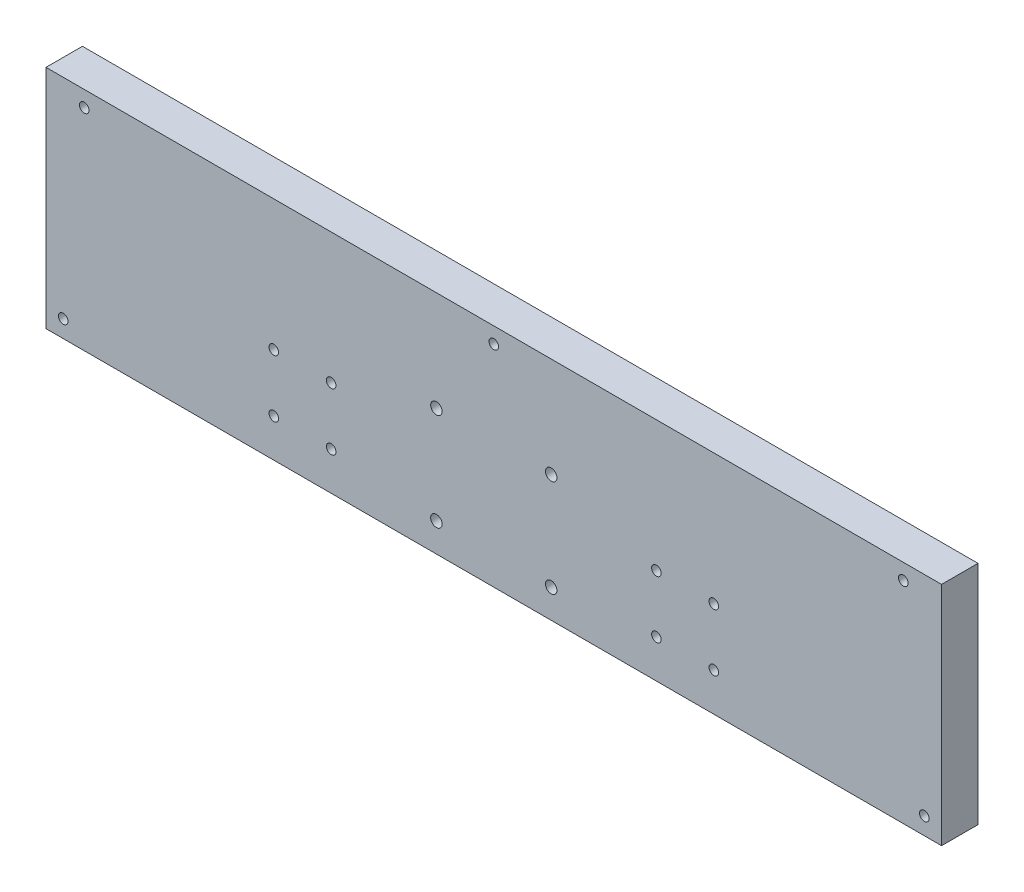
SolidWorks part; units mm, degrees
ref_plane "Front Plane" through (0, 0, 0) normal (0, 0, 1) x (1, 0, 0)
ref_plane "Top Plane" through (0, 0, 0) normal (0, 1, 0) x (1, 0, 0)
ref_plane "Right Plane" through (0, 0, 0) normal (1, 0, 0) x (0, 0, -1)
sketch "Sketch1" plane through (0, 0, 0) normal (0, 0, 1) x (1, 0, 0)
  line L1 (234.05, 0) -> (-234.05, 0)
  line L2 (234.05, 0) -> (234.05, 118.3)
  line L3 (234.05, 118.3) -> (-234.05, 118.3)
  line L4 (-234.05, 0) -> (-234.05, 118.3)
  line L5 (-234.05, 118.3) -> (234.05, 118.3) construction
  dimension "D1" = 118.3
  dimension "D2" = 468.1
extrude "Boss-Extrude1" add sketch "Sketch1" along normal blind 19.05
sketch "Sketch8" plane through (0, 0, 19.05) normal (0, 0, 1) x (1, 0, 0)
  circle A0 centre (-214.05, 110.05) radius 2.5
  circle A1 centre (0, 110.05) radius 2.5
  circle A2 centre (214.05, 110.05) radius 2.5
  circle A3 centre (-225.05, 9) radius 2.5
  circle A4 centre (225.05, 9) radius 2.5
hole_wizard "M5 Clearance Hole1" positions "Sketch2" profile "Sketch3" hole size "M5" standard "ANSI Metric"
sketch "Sketch2" plane through (0, 0, 0) normal (0, 0, -1) x (-1, 0, 0)
  point P0 (-115, 20)
  point P3 (-115, 50)
  point P6 (-85, 50)
  point P9 (-85, 20)
  point P12 (85, 20)
  point P15 (85, 50)
  point P18 (115, 50)
  point P21 (115, 20)
  point P25 (214.05, 110.05)
  point P28 (0, 110.05)
  point P31 (-214.05, 110.05)
  point P34 (-225.05, 9)
  point P37 (225.05, 9)
sketch "Sketch3" plane through (115, 20, 0) normal (1, 0, 0) x (0, 1, 0)
  line L0 (0, 0) -> (0, 30)
  line L1 (0, 30) -> (2.5, 28.4978)
  line L2 (2.5, 28.4978) -> (2.5, 0)
  line L5 (2.5, 0) -> (0, 0)
  line L10 (0, 30) -> (-2.5, 28.4978) construction
  line L11 (0, -6.35) -> (0, 107.95) construction
  dimension "Hole Dia." = 5
  dimension "Hole Depth" = 30
  dimension "Drill Angle" = 118
sketch "Sketch4" plane through (0, 0, 0) normal (0, 0, -1) x (-1, 0, 0)
  circle A0 centre (-30, 15) radius 3 construction
  circle A1 centre (-30, 66) radius 3 construction
  circle A2 centre (30, 66) radius 3 construction
  circle A3 centre (30, 15) radius 3 construction
  circle A4 centre (-30, 15) radius 3
  circle A5 centre (-30, 66) radius 3
  circle A6 centre (30, 66) radius 3
  circle A7 centre (30, 15) radius 3
hole_wizard "M5 Clearance Hole2" positions "Sketch5" profile "Sketch6" hole size "M5" standard "ANSI Metric"
sketch "Sketch5" plane through (0, 0, 0) normal (0, 0, -1) x (-1, 0, 0)
  point P0 (30, 15)
  point P3 (30, 66)
  point P6 (-30, 15)
  point P9 (-30, 66)
sketch "Sketch6" plane through (-30, 15, 0) normal (1, 0, 0) x (0, 1, 0)
  line L0 (0, 0) -> (0, 30)
  line L1 (0, 30) -> (3, 28.1974)
  line L2 (3, 28.1974) -> (3, 0)
  line L5 (3, 0) -> (0, 0)
  line L10 (0, 30) -> (-3, 28.1974) construction
  line L11 (0, -6.35) -> (0, 107.95) construction
  dimension "Hole Dia." = 6
  dimension "Hole Depth" = 30
  dimension "Drill Angle" = 118
